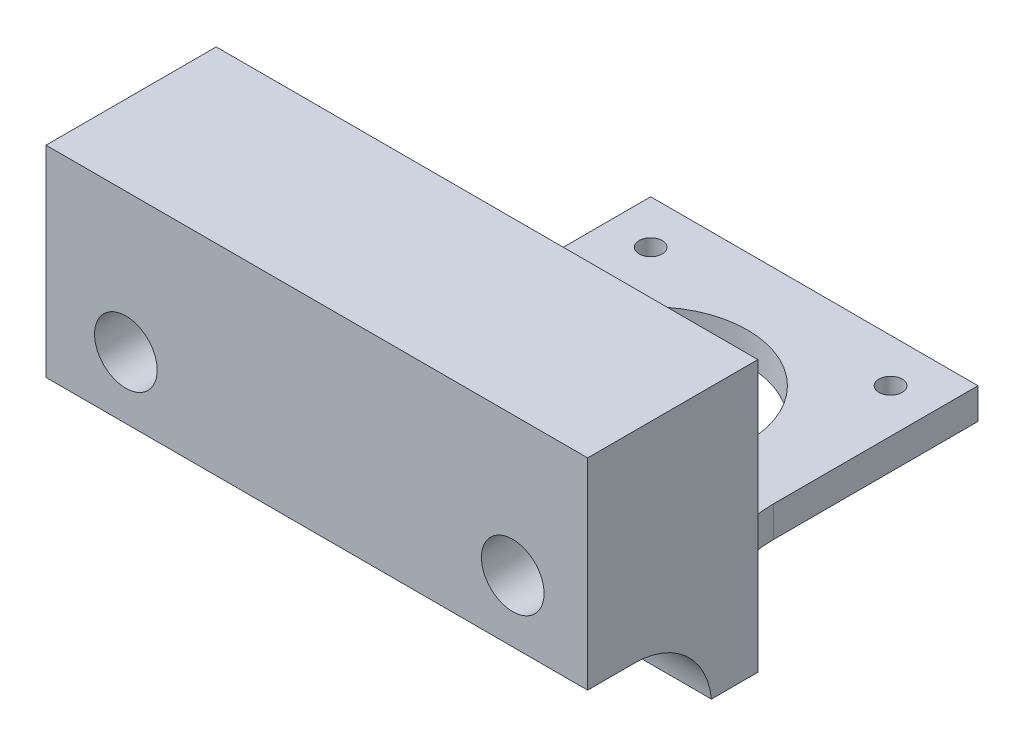
SolidWorks part; units mm, degrees
note: The reader was unsure of these and kept them because the rebuilt part matched: shared geometry of "Sketch5<2>".
ref_plane "Front Plane" through (0, 0, 0) normal (0, 0, 1) x (1, 0, 0)
ref_plane "Top Plane" through (0, 0, 0) normal (0, 1, 0) x (1, 0, 0)
ref_plane "Right Plane" through (0, 0, 0) normal (1, 0, 0) x (0, 0, -1)
sketch "Sketch1" plane through (0, 0, 0) normal (0, 1, 0) x (1, 0, 0)
  line L1 (-15.5, 15.5) -> (15.5, 15.5)
  line L2 (-15.5, 15.5) -> (-15.5, -15.5)
  line L3 (-15.5, -15.5) -> (15.5, -15.5)
  line L4 (15.5, 15.5) -> (15.5, -15.5)
  line L5 (-15.5, 15.5) -> (15.5, -15.5) construction
  line L6 (-15.5, -15.5) -> (15.5, 15.5) construction
  line L7 (-21.15, 21.15) -> (21.15, 21.15)
  line L8 (-21.15, 21.15) -> (-21.15, -21.15)
  line L9 (-21.15, -21.15) -> (21.15, -21.15)
  line L10 (21.15, 21.15) -> (21.15, -21.15)
  line L11 (-21.15, 21.15) -> (21.15, -21.15) construction
  line L12 (-21.15, -21.15) -> (21.15, 21.15) construction
  circle A0 centre (-15.5, 15.5) radius 1.5
  circle A1 centre (15.5, 15.5) radius 1.5
  circle A2 centre (15.5, -15.5) radius 1.5
  circle A3 centre (-15.5, -15.5) radius 1.5
  circle A4 centre (0, 0) radius 12.5
  point P0 (0, 0)
  point P6 (0, 0)
  dimension "D5" = 3
  dimension "D6" = 25
  dimension "D1" = 42.3
  dimension "D2" = 42.3
  dimension "D3" = 31
  dimension "D4" = 31
extrude "Boss-Extrude1" add sketch "Sketch1" along normal blind 4 contours A4 | L1 A0 L2 | L2 A0 L1 | L3 A2 L4 | L4 A2 L3 | L2 A3 L3 | L3 A3 L2 | L7 L10 L9 L8 | A1
sketch "Sketch2" plane through (0, 0, 21.15) normal (0, 0, 1) x (1, 0, 0)
  line L1 (-35, 0) -> (35, 0)
  line L2 (-35, 0) -> (-35, 35)
  line L3 (-35, 35) -> (35, 35)
  line L4 (35, 0) -> (35, 35)
  line L6 (-35, 35) -> (35, 35)
  line L7 (-35, 35) -> (-35, 16)
  line L8 (-35, 16) -> (35, 16)
  line L9 (35, 35) -> (35, 16)
  dimension "D3" = 35
  dimension "D1" = 70
  dimension "D2" = 35
  dimension "D7" = 19
extrude "Boss-Extrude3" add sketch "Sketch2" along normal blind 6
sketch "Sketch5" plane through (0, 0, 27.15) normal (0, 0, 1) x (1, 0, 0)
  line L0 (35, 0) -> (35, 35) construction
  line L1 (-35, 35) -> (35, 35)
  line L2 (-35, 35) -> (-35, 9)
  line L3 (-35, 9) -> (35, 9)
  line L4 (35, 35) -> (35, 9)
  line L5 (-35, 0) -> (35, 0) construction
  circle A0 centre (-24.679, 17) radius 4.05
  circle A1 centre (25.321, 17) radius 4.05
  dimension "D2" = 8.1
  dimension "D1" = 26
  dimension "D3" = 18
  dimension "D4" = 50
extrude "Boss-Extrude7" add sketch "Sketch5" along normal blind 16
extrude "Cut-Extrude1" cut sketch "Sketch5<2>" against normal blind 16 contours A0 | A1
sketch "Sketch5<2>" plane through (0, 0, 27.15) normal (0, 0, 1) x (1, 0, 0) same geometry as "Sketch5"
fillet "Fillet1" radius 16 2 edges
fillet "Fillet2" radius 10 1 edges
fillet "Fillet4" radius 2 1 edges at (0, 4, 21.15)
